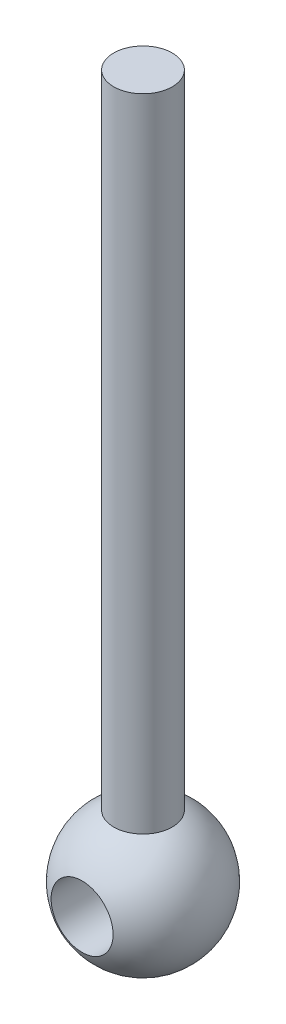
SolidWorks part; units mm, degrees
material "Plain Carbon Steel"
ref_plane "Front Plane" through (0, 0, 0) normal (0, 0, 1) x (1, 0, 0)
ref_plane "Top Plane" through (0, 0, 0) normal (0, 1, 0) x (1, 0, 0)
ref_plane "Right Plane" through (0, 0, 0) normal (1, 0, 0) x (0, 0, -1)
sketch "Sketch1" plane through (0, 0, 0) normal (0, 1, 0) x (1, 0, 0)
  line L0 (0, -6.2385) -> (0, 6.2385) construction
  line L1 (3.175, 6.2385) -> (3.175, -6.2385)
  arc A0 (3.175, -6.2385) -> (3.175, 6.2385) centre (0, 0) ccw
  dimension "D1" = 7
  dimension "D2" = 3.175
revolve "Revolve1" add sketch "Sketch1" angle 360 about L0
sketch "Sketch2" plane through (0, 0, 0) normal (0, 1, 0) x (1, 0, 0)
  circle A0 centre (0, 0) radius 3
  dimension "D1" = 6
extrude "Boss-Extrude1" add sketch "Sketch2" along normal blind 68.5 from offset 3.5
